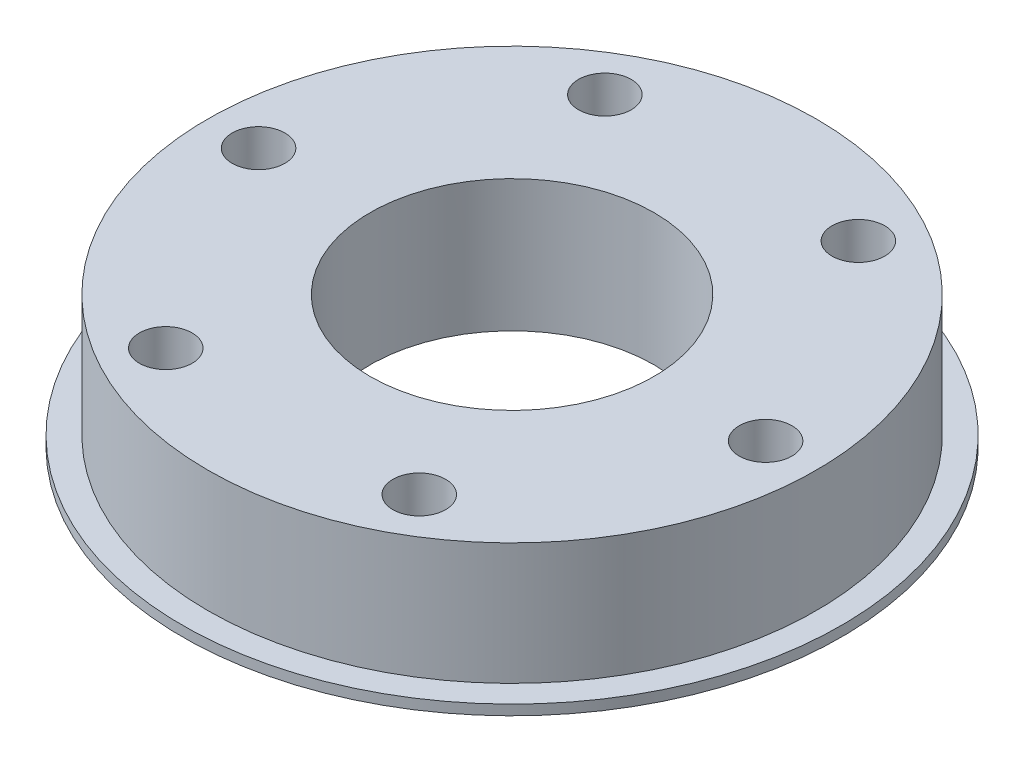
SolidWorks part; units mm, degrees
ref_plane "Front Plane" through (0, 0, 0) normal (0, 0, 1) x (1, 0, 0)
ref_plane "Top Plane" through (0, 0, 0) normal (0, 1, 0) x (1, 0, 0)
ref_plane "Right Plane" through (0, 0, 0) normal (1, 0, 0) x (0, 0, -1)
sketch "Sketch1" plane through (0, 0, 0) normal (0, 1, 0) x (1, 0, 0)
  circle A0 centre (0, 0) radius 30
  point P18 (0, 0)
  dimension "D4" = 60
extrude "Boss-Extrude1" add sketch "Sketch1" along normal blind 13
sketch "Sketch2" plane through (0, 0, 0) normal (0, -1, 0) x (1, 0, 0)
  circle A0 centre (0, 0) radius 32.5
  dimension "D1" = 65
extrude "Boss-Extrude2" add sketch "Sketch2" against normal blind 1
sketch "Sketch3" plane through (0, 0, 0) normal (0, 1, 0) x (1, 0, 0)
  circle A1 centre (0, 0) radius 25 construction
  circle A2 centre (0, 25) radius 1.75
  circle A3 centre (21.6506, 12.5) radius 1.75
  circle A4 centre (21.6506, -12.5) radius 1.75
  circle A5 centre (0, -25) radius 1.75
  circle A6 centre (-21.6506, -12.5) radius 1.75
  circle A7 centre (-21.6506, 12.5) radius 1.75
  point P30 (0, 0)
  dimension "D1" = 50
  dimension "D2" = 3.5
  dimension "D3" = 6
extrude "Cut-Extrude1" cut sketch "Sketch3" along normal blind 3.5
sketch "Sketch4" plane through (0, 0, 0) normal (0, -1, 0) x (1, 0, 0)
  circle A0 centre (0, 0) radius 14
  dimension "D1" = 28
extrude "Cut-Extrude2" cut sketch "Sketch4" against normal blind 51
sketch "Sketch5" plane through (0, 0, 0) normal (0, -1, 0) x (1, 0, 0)
  line L0 (-12.5, 21.6506) -> (0, 0) construction
  line L1 (0, 0) -> (0, 25) construction
  line L2 (0, 25) -> (-21.6506, 12.5) construction
  circle A0 centre (0, 0) radius 25 construction
  circle A1 centre (-12.5, 21.6506) radius 2.6
  circle A2 centre (12.5, 21.6506) radius 2.6
  circle A3 centre (25, 0) radius 2.6
  circle A4 centre (12.5, -21.6506) radius 2.6
  circle A5 centre (-12.5, -21.6506) radius 2.6
  circle A6 centre (-25, 0) radius 2.6
  point P21 (0, 0)
  dimension "D1" = 5.2
  dimension "D2" = 6
extrude "Cut-Extrude3" cut sketch "Sketch5" against normal blind 25
